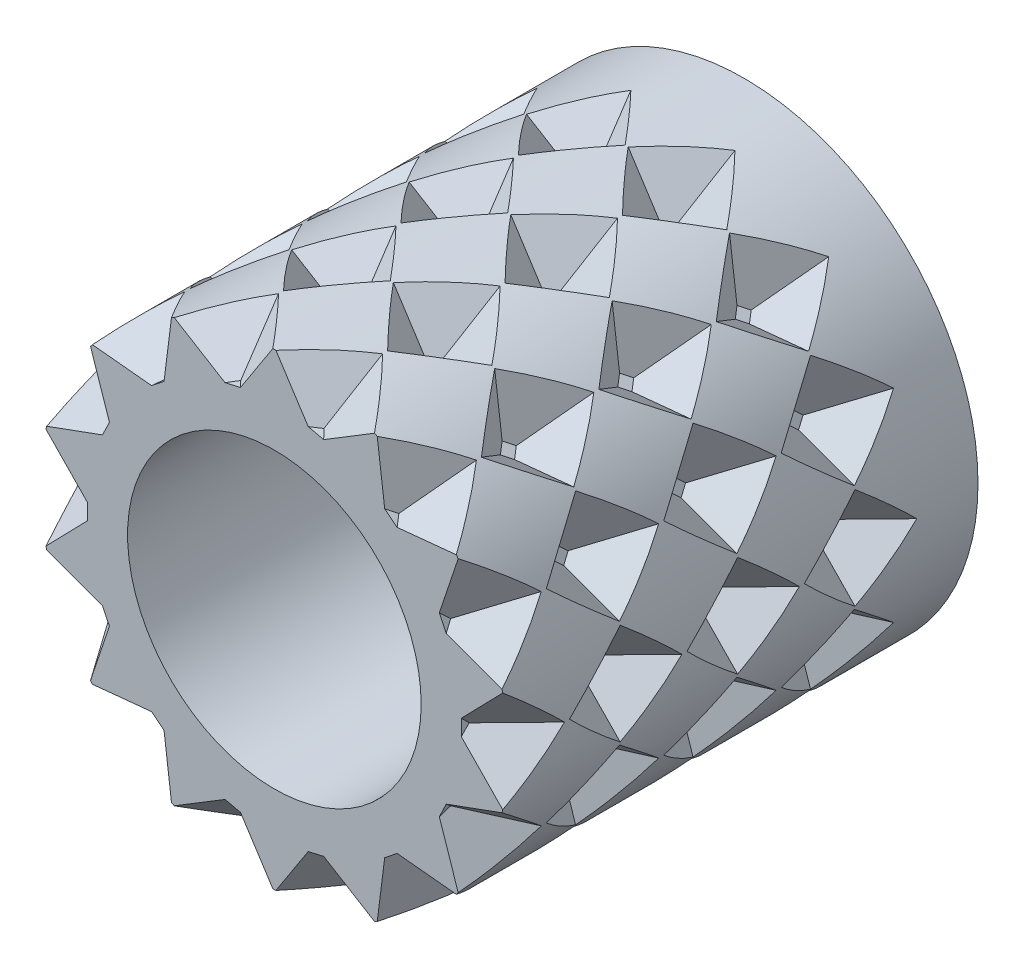
SolidWorks part; units mm, degrees
ref_plane "Front Plane" through (0, 0, 0) normal (0, 0, 1) x (1, 0, 0)
ref_plane "Top Plane" through (0, 0, 0) normal (0, 1, 0) x (1, 0, 0)
ref_plane "Right Plane" through (0, 0, 0) normal (1, 0, 0) x (0, 0, -1)
sketch "Sketch1" plane through (0, 0, 0) normal (0, 0, 1) x (1, 0, 0)
  circle A0 centre (0, 0) radius 1.5
  circle A1 centre (0, 0) radius 2.39
  dimension "D1" = 4.78
  dimension "D2" = 3
extrude "Boss-Extrude1" add sketch "Sketch1" along normal blind 4.8
ref_plane "Plane1" through (2.41, 0, 0) normal (1, 0, 0) x (0, 0, -1)
sketch "Sketch5" plane through (2.41, 0, 0) normal (1, 0, 0) x (0, 0, -1)
  line L0 (-4.8, 2.39) -> (-4.8, -2.39) construction
  line L1 (-4.8, 0.595) -> (-5.395, 0)
  line L2 (-5.395, 0) -> (-4.8, -0.595)
  line L3 (-4.8, -0.595) -> (-4.205, 0)
  line L4 (-4.205, 0) -> (-4.8, 0.595)
  line L5 (-4.8, 0) -> (0, 0) construction
  line L6 (-3.005, 0) -> (-3.6, 0.595)
  line L7 (-3.6, 0.595) -> (-4.195, 0)
  line L8 (-3.6, -0.595) -> (-3.005, 0)
  line L9 (-4.195, 0) -> (-3.6, -0.595)
  line L10 (-1.805, 0) -> (-2.4, 0.595)
  line L11 (-2.4, 0.595) -> (-2.995, 0)
  line L12 (-2.4, -0.595) -> (-1.805, 0)
  line L13 (-2.995, 0) -> (-2.4, -0.595)
  line L14 (-0.605, 0) -> (-1.2, 0.595)
  line L15 (-1.2, 0.595) -> (-1.795, 0)
  line L16 (-1.2, -0.595) -> (-0.605, 0)
  line L17 (-1.795, 0) -> (-1.2, -0.595)
  line L18 (0.595, 0) -> (0, 0.595)
  line L19 (0, 0.595) -> (-0.595, 0)
  line L20 (0, -0.595) -> (0.595, 0)
  line L21 (-0.595, 0) -> (0, -0.595)
  circle A0 centre (-4.8, 0) radius 0.4207 construction
  dimension "D1" = 1.19
  dimension "D2" = 5
extrude "Cut-Extrude1" cut sketch "Sketch5" against normal blind 0.5 draft 36
pattern_circular "CirPattern1" count 14 over 360 about axis through (0, 0, 0) along (0, 0, 1) of "Cut-Extrude1"
sketch "Sketch6" plane through (0, 0, 0) normal (0, 0, -1) x (-1, 0, 0)
  circle A0 centre (0, 0) radius 2.39
  circle A1 centre (0, 0) radius 1.5
extrude "Boss-Extrude2" add sketch "Sketch6" against normal blind 0.6
